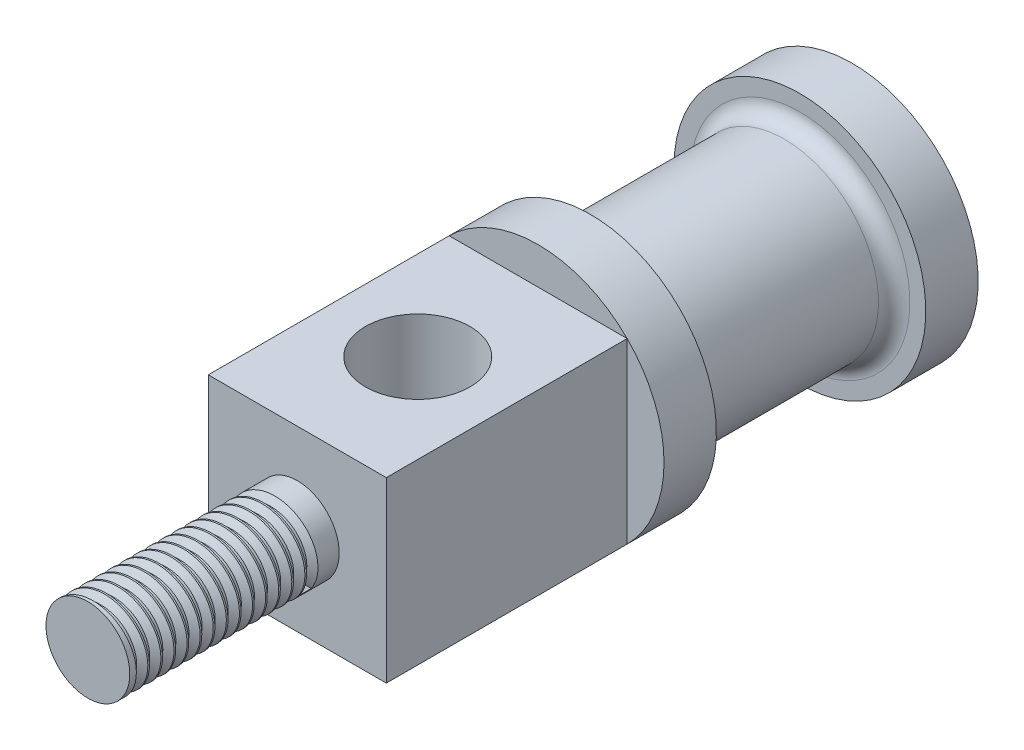
SolidWorks part; units mm, degrees
ref_plane "Front Plane" through (0, 0, 0) normal (0, 0, 1) x (1, 0, 0)
ref_plane "Top Plane" through (0, 0, 0) normal (0, 1, 0) x (1, 0, 0)
ref_plane "Right Plane" through (0, 0, 0) normal (1, 0, 0) x (0, 0, -1)
sketch "Sketch1" plane through (0, 0, 0) normal (0, 0, 1) x (1, 0, 0)
  line L1 (0, 0) -> (17, 0)
  line L2 (0, 0) -> (0, 17)
  line L3 (0, 17) -> (17, 17)
  line L4 (17, 0) -> (17, 17)
  dimension "D1" = 17
extrude "Boss-Extrude1" add sketch "Sketch1" along normal blind 23
sketch "Sketch2" plane through (0, 0, 23) normal (0, 0, 1) x (1, 0, 0)
  line L0 (8.5, 17) -> (8.5, 0) construction
  line L1 (17, 17) -> (0, 17) construction
  line L2 (0, 0) -> (17, 0) construction
  circle A0 centre (8.5, 8.5) radius 4
extrude "Boss-Extrude2" add sketch "Sketch2" along normal blind 20
sketch "Sketch3" plane through (0, 0, 0) normal (0, 0, -1) x (-1, 0, 0)
  line L0 (-8.5, 17) -> (-8.5, 0) construction
  line L1 (-17, 17) -> (0, 17) construction
  line L2 (0, 0) -> (-17, 0) construction
  circle A0 centre (-8.5, 8.5) radius 12.0208
extrude "Boss-Extrude3" add sketch "Sketch3" along normal blind 5
sketch "Sketch4" plane through (0, 0, -5) normal (0, 0, -1) x (-1, 0, 0)
  circle A0 centre (-8.5, 8.5) radius 9
extrude "Boss-Extrude4" add sketch "Sketch4" along normal blind 20
sketch "Sketch5" plane through (0, 0, -25) normal (0, 0, -1) x (-1, 0, 0)
  circle A0 centre (-8.5, 8.5) radius 12.0208
extrude "Boss-Extrude5" add sketch "Sketch5" along normal blind 5
thread "Thread1" pitch 1.25 method cut profile "Thread Profile1" start angle 0, offset 0, length 17, pitch 1.25, diameter 8
ref_plane "Plane1" through (4.5, 8.5, 43) normal (0, -1, 0) x (-1, 0, 0)
sketch "Thread Profile1" plane through (4.5, 8.5, 43) normal (0, -1, 0) x (-1, 0, 0)
  line L0 (0, 0) -> (0, 1.25) construction
  line L11 (0, 0) -> (0, 1.0937)
  line L12 (0, 1.0937) -> (-0.6766, 0.7031)
  line L13 (-0.6766, 0.7031) -> (-0.6766, 0.3906)
  line L15 (-0.6766, 0.3906) -> (0, 0)
  line L17 (-0.6766, 0.5469) -> (0, 0.5469) construction
  point P2 (0, 0)
  dimension "Pitch" = 1.25
  dimension "Profile_Angle" = 60
  dimension "Profile_Land" = 0.3125
  dimension "Profile_Height" = 0.6766
sketch "Sketch9" plane through (0, 17, 0) normal (0, 1, 0) x (1, 0, 0)
  line L0 (8.5, -23) -> (8.5, 0) construction
  line L1 (17, -23) -> (0, -23) construction
  line L2 (0, 0) -> (17, 0) construction
  circle A0 centre (8.5, -11.5) radius 5
extrude "Cut-Extrude1" cut sketch "Sketch9" against normal blind 20
fillet "Fillet1" radius 1.5 2 edges at (-0.5, 8.5, -5) (-0.5, 8.5, -25)
